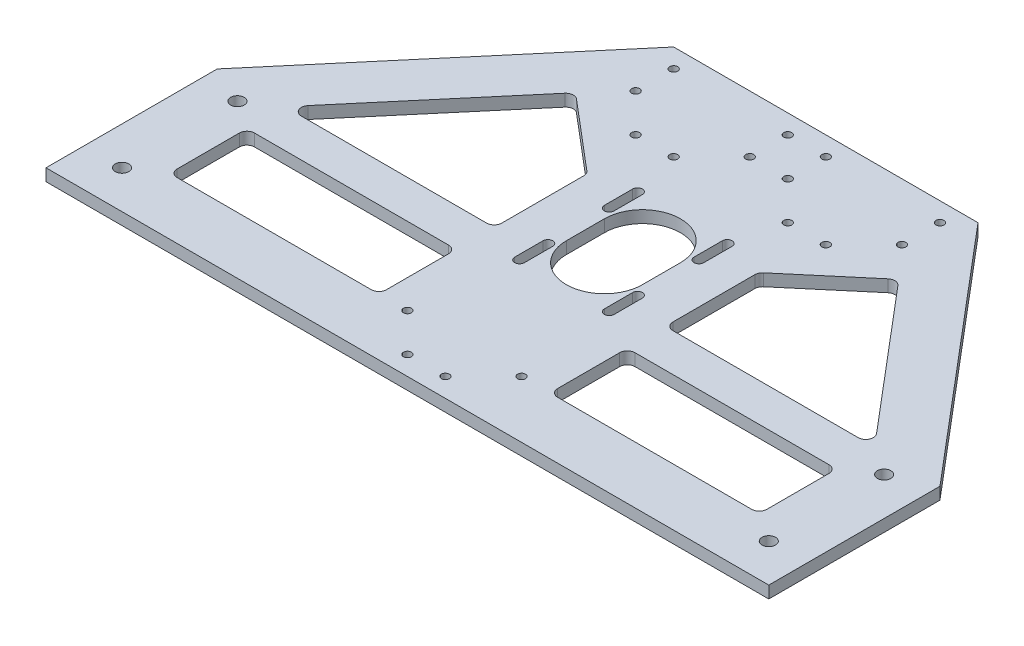
SolidWorks part; units mm, degrees
ref_plane "Front Plane" through (0, 0, 0) normal (0, 0, 1) x (1, 0, 0)
ref_plane "Top Plane" through (0, 0, 0) normal (0, 1, 0) x (1, 0, 0)
ref_plane "Right Plane" through (0, 0, 0) normal (1, 0, 0) x (0, 0, -1)
sketch "Sketch1" plane through (0, 0, 0) normal (0, 1, 0) x (1, 0, 0)
  line L0 (0, 0) -> (160, 0)
  line L1 (160, 0) -> (270, -130)
  line L2 (270, -130) -> (270, -220)
  line L3 (270, -220) -> (-110, -220)
  line L4 (-110, -220) -> (-110, -130)
  line L5 (-110, -130) -> (0, 0)
  dimension "D1" = 160
  dimension "D2" = 380
  dimension "D3" = 110
  dimension "D4" = 220
  dimension "D5" = 90
extrude "Boss-Extrude1" add sketch "Sketch1" along normal blind 6.35
hole_wizard "M5x0.8 Tapped Hole1" positions "Sketch3" profile "Sketch2" tap size "M5x0.8" standard "ANSI Metric" end condition through all
sketch "Sketch3" plane through (0, 6.35, 0) normal (0, 1, 0) x (1, 0, 0)
  line L1 (-110, -130) -> (-110, -220) construction
  line L3 (160, 0) -> (0, 0) construction
  line L4 (-110, -220) -> (270, -220) construction
  point P0 (10, -10)
  point P2 (150, -10)
  point P4 (150, -30)
  point P6 (10, -30)
  point P8 (30, -50)
  point P10 (50, -50)
  point P45 (110, -50)
  point P47 (130, -50)
  point P49 (90, -10)
  point P51 (90, -30)
  point P53 (70, -10)
  point P55 (70, -30)
  point P56 (70, -210)
  point P58 (90, -210)
  point P60 (50, -190)
  point P62 (110, -190)
  dimension "D1" = 140
  dimension "D2" = 10
  dimension "D3" = 20
  dimension "D4" = 20
  dimension "D5" = 20
  dimension "D6" = 120
  dimension "D7" = 20
  dimension "D8" = 20
  dimension "D9" = 20
  dimension "D10" = 20
  dimension "D11" = 20
  dimension "D12" = 20
  dimension "D13" = 20
  dimension "D14" = 20
  dimension "D15" = 10
  dimension "D16" = 20
  dimension "D17" = 20
sketch "Sketch2" plane through (10, 6.35, 10) normal (1, 0, 0) x (0, 0, 1)
  line L0 (0, 0) -> (0, 6.35)
  line L1 (0, 6.35) -> (2.1, 6.35)
  line L2 (2.1, 6.35) -> (2.1, 0)
  line L5 (2.1, 0) -> (0, 0)
  line L11 (0, -6.35) -> (0, 107.95) construction
  dimension "Thru Tap Drill Dia." = 4.2
  dimension "Thru Tap Drill Depth" = 6.35
cosmetic thread "Hole Thread1" parameters "D2"=5
cosmetic thread "Hole Thread2" parameters "D2"=5
cosmetic thread "Hole Thread3" parameters "D2"=5
cosmetic thread "Hole Thread4" parameters "D2"=5
cosmetic thread "Hole Thread5" parameters "D2"=5
cosmetic thread "Hole Thread6" parameters "D2"=5
cosmetic thread "Hole Thread7" parameters "D2"=5
cosmetic thread "Hole Thread8" parameters "D2"=5
cosmetic thread "Hole Thread9" parameters "D2"=5
cosmetic thread "Hole Thread10" parameters "D2"=5
cosmetic thread "Hole Thread11" parameters "D2"=5
cosmetic thread "Hole Thread12" parameters "D2"=5
cosmetic thread "Hole Thread13" parameters "D2"=5
cosmetic thread "Hole Thread14" parameters "D2"=5
cosmetic thread "Hole Thread15" parameters "D2"=5
cosmetic thread "Hole Thread16" parameters "D2"=5
hole_wizard "Ø7.1 (7.1) Diameter Hole1" positions "Sketch6" profile "Sketch5" hole size "Ø7.1" standard "ANSI Metric" end condition through all
sketch "Sketch6" plane through (0, 6.35, 0) normal (0, 1, 0) x (1, 0, 0)
  line L0 (-110, -130) -> (-110, -220) construction
  line L1 (-110, -220) -> (270, -220) construction
  point P0 (250, -139.36)
  point P2 (250, -200)
  point P4 (-90, -200)
  point P6 (-90, -139.36)
  dimension "D1" = 60.64
  dimension "D2" = 20
  dimension "D3" = 20
  dimension "D4" = 360
sketch "Sketch5" plane through (250, 6.35, 139.36) normal (1, 0, 0) x (0, 0, 1)
  line L0 (0, 0) -> (0, 6.35)
  line L1 (0, 6.35) -> (3.55, 6.35)
  line L2 (3.55, 6.35) -> (3.55, 0)
  line L5 (3.55, 0) -> (0, 0)
  line L11 (0, -6.35) -> (0, 107.95) construction
  dimension "Thru Hole Dia." = 7.1
  dimension "Thru Hole Depth" = 6.35
sketch "Sketch12" plane through (0, 6.35, 0) normal (0, 1, 0) x (1, 0, 0)
  line L0 (-110, -130) -> (-110, -220) construction
  line L1 (-110, -220) -> (270, -220) construction
  point P0 (56.43, -130)
  point P1 (103.57, -130)
  point P2 (103.57, -82.86)
  point P3 (56.43, -82.86)
  point P4 (80, -106.43)
  dimension "D1" = 47.14
  dimension "D2" = 47.14
  dimension "D3" = 166.43
  dimension "D4" = 90
  dimension "D5" = 23.57
  dimension "D6" = 23.57
hole_wizard "Ø5.0mm Clearance Dowel Slot2" positions "Sketch16" profile "Sketch15" size "Ø5.0" standard "ANSI Metric" slot yes end condition through all
sketch "Sketch16" plane through (0, 6.35, 0) normal (0, 1, 0) x (1, 0, 0)
  line L0 (56.43, -140) -> (56.43, -120) construction
  point P0 (56.43, -130)
  point P5 (103.57, -130)
  point P8 (103.57, -82.86)
  point P11 (56.43, -82.86)
  dimension "D1" = 20
sketch "Sketch15" plane through (56.43, 6.35, 130) normal (1, 0, 0) x (0, 0, 1)
  line L0 (0, 0) -> (0, 6.35)
  line L1 (0, 6.35) -> (2.55, 6.35)
  line L2 (2.55, 6.35) -> (2.55, 0)
  line L5 (2.55, 0) -> (0, 0)
  line L11 (0, -6.35) -> (0, 107.95) construction
  dimension "Thru Hole Dia." = 5.1
  dimension "Thru Hole Depth" = 6.35
sketch "Sketch17" plane through (0, 6.35, 0) normal (0, 1, 0) x (1, 0, 0)
  line L0 (80, -96.43) -> (80, -116.43) construction
  line L1 (100, -96.43) -> (100, -116.43)
  line L2 (60, -96.43) -> (60, -116.43)
  arc A0 (100, -96.43) -> (60, -96.43) centre (80, -96.43) ccw
  arc A1 (60, -116.43) -> (100, -116.43) centre (80, -116.43) ccw
  point P2 (80, -106.43)
  dimension "D1" = 20
  dimension "D2" = 20
extrude "Cut-Extrude1" cut sketch "Sketch17" against normal blind 10
sketch "Sketch18" plane through (0, 6.35, 0) normal (0, 1, 0) x (1, 0, 0)
  line L0 (-75, -129.36) -> (-4.9758, -46.6041)
  line L1 (-75, -149.36) -> (35, -149.36)
  line L2 (-75, -149.36) -> (-75, -190)
  line L3 (-75, -190) -> (35, -190)
  line L4 (35, -149.36) -> (35, -190)
  line L5 (-4.9758, -46.6041) -> (35, -80.4298)
  line L6 (35, -80.4298) -> (35, -129.36)
  line L7 (35, -129.36) -> (-75, -129.36)
  line L8 (0, 0) -> (-110, -130) construction
  circle A0 centre (-90, -139.36) radius 3.55 construction
  circle A1 centre (50, -190) radius 2.1 construction
  circle A2 centre (-90, -200) radius 3.55 construction
  circle A4 centre (30, -50) radius 2.1 construction
  dimension "D4" = 10
  dimension "D6" = 20
  dimension "D1" = 15
  dimension "D2" = 15
  dimension "D3" = 10
  dimension "D5" = 10
extrude "Cut-Extrude2" cut sketch "Sketch18" against normal blind 10
fillet "Fillet1" radius 4 8 edges at (35, 3.175, 149.36) (-75, 3.175, 149.36) (-75, 3.175, 190) (35, 3.175, 190) (35, 3.175, 129.36) (-75, 3.175, 129.36) (-4.9758, 3.175, 46.6041) (35, 3.175, 80.4298)
ref_plane "Plane1" through (80, 0, 0) normal (-1, 0, 0) x (0, 0, 1)
mirror "Mirror1" about plane through (80, 0, 0) normal (-1, 0, 0) of "Fillet1", "Cut-Extrude2"
